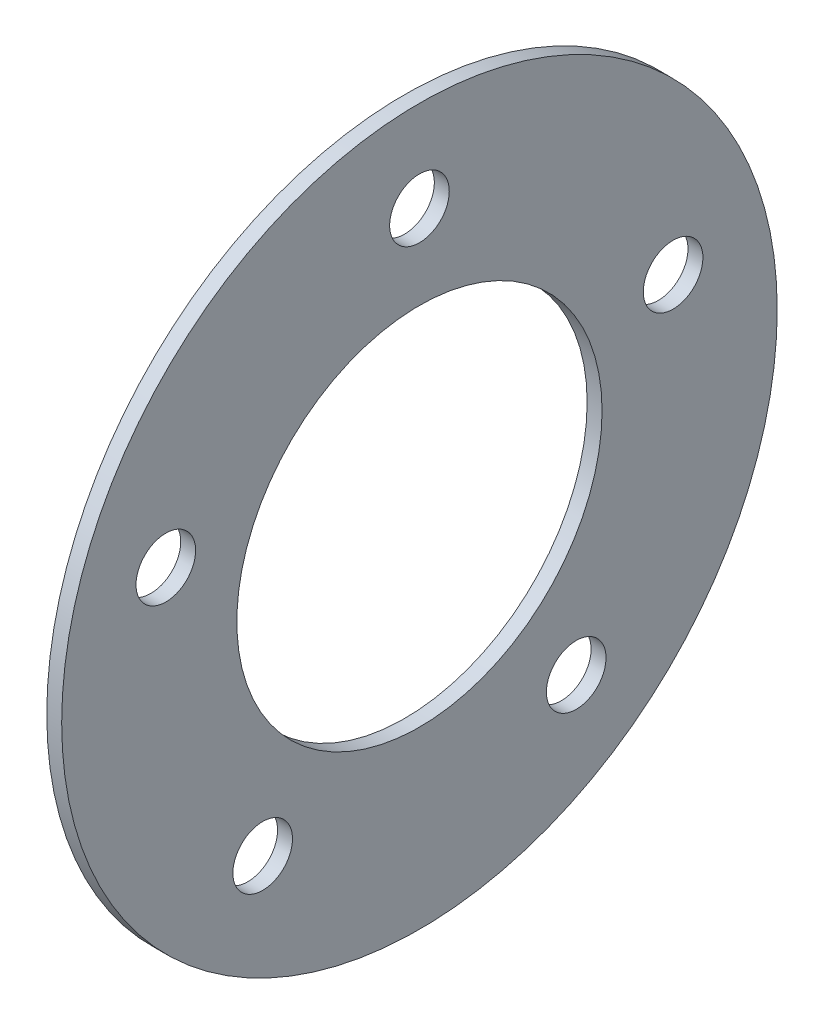
SolidWorks part; units mm, degrees
material "ASTM A36 Steel"
ref_plane "Front Plane" through (0, 0, 0) normal (0, 0, 1) x (1, 0, 0)
ref_plane "Top Plane" through (0, 0, 0) normal (0, 1, 0) x (1, 0, 0)
ref_plane "Right Plane" through (0, 0, 0) normal (1, 0, 0) x (0, 0, -1)
sketch "Sketch1" plane through (0, 0, 0) normal (1, 0, 0) x (0, 0, -1)
  circle A0 centre (0, 0) radius 76.2
  circle A1 centre (0, 0) radius 38.8938
  dimension "D1" = 152.4
  dimension "D2" = 77.7875
extrude "Boss-Extrude1" add sketch "Sketch1" along normal mid plane 3.175
sketch "Sketch3" plane through (1.5875, 0, 0) normal (1, 0, 0) x (0, 0, -1)
  line L0 (0, 1.7463) -> (0, -1.7463) construction
  line L1 (1.7463, 0) -> (-1.7463, 0) construction
  circle A0 centre (0, 56.7995) radius 6.35
  dimension "D2" = 12.7
  dimension "D1" = 56.7995
extrude "Cut-Extrude1" cut sketch "Sketch3" against normal through all
ref_axis "Axis1" through (-1.7463, 0, 0) along (1, 0, 0)
pattern_circular "CirPattern1" count 5 over 360 about axis through (-1.7463, 0, 0) along (1, 0, 0) of "Cut-Extrude1"
